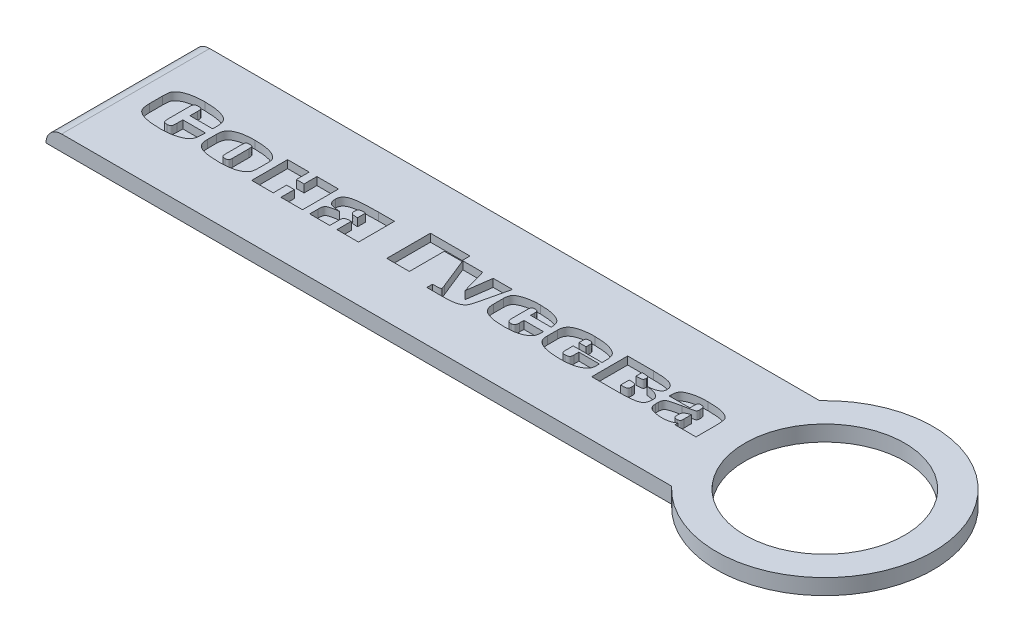
SolidWorks part; units mm, degrees
ref_plane "Спереди" through (0, 0, 0) normal (0, 0, 1) x (1, 0, 0)
ref_plane "Сверху" through (0, 0, 0) normal (0, 1, 0) x (1, 0, 0)
ref_plane "Справа" through (0, 0, 0) normal (1, 0, 0) x (0, 0, -1)
other "Configuration Table"
sketch "Эскиз1" plane through (0, 0, 0) normal (0, 1, 0) x (1, 0, 0)
  line L0 (-1.8872, 9.4545) -> (104.9832, 9.4545) construction
  line L1 (0, 0) -> (80, 0)
  line L2 (0, 0) -> (0, 18.9091)
  line L3 (0, 18.9091) -> (80, 18.9091)
  line L4 (80, 0) -> (80, 18.9091)
  circle A0 centre (90.0343, 9.4545) radius 13.8498
  dimension "D1" = 80
extrude "Бобышка-Вытянуть5" add sketch "Эскиз1" along normal blind 2 contours L0 L4 L1 A0 | L4 L0 A0 L3 | L1 L4 L3 L2 | A0 region at (91.0838, 0, -15.534) region at (91.0838, 0, -3.3751)
sketch "Эскиз2" plane through (0, 2, 0) normal (0, 1, 0) x (1, 0, 0)
  line L0 (90.0343, 23.3043) -> (90.0343, -4.3952) construction
  arc A0 (79.9137, 0) -> (79.9137, 18.9091) centre (90.0343, 9.4545) ccw construction
  circle A1 centre (90.0343, 9.4545) radius 10.1983
extrude "Вырез-Вытянуть1" cut sketch "Эскиз2" against normal blind 3
sketch "Эскиз3" plane through (0, 2, 0) normal (0, 1, 0) x (1, 0, 0)
  line L0 (0, 7) -> (76.4904, 7) construction
  line L1 (0, 0) -> (0, 18.9091) construction
  line L2 (0, 0) -> (79.9137, 0) construction
  text T0 "Соня Гусева" font "Impact" height in points 20
  dimension "D1" = 7
extrude "надпись" cut sketch "Эскиз3" against normal blind 1
fillet "Скругление3" radius 2 1 edges at (0, 2, -9.4545)
